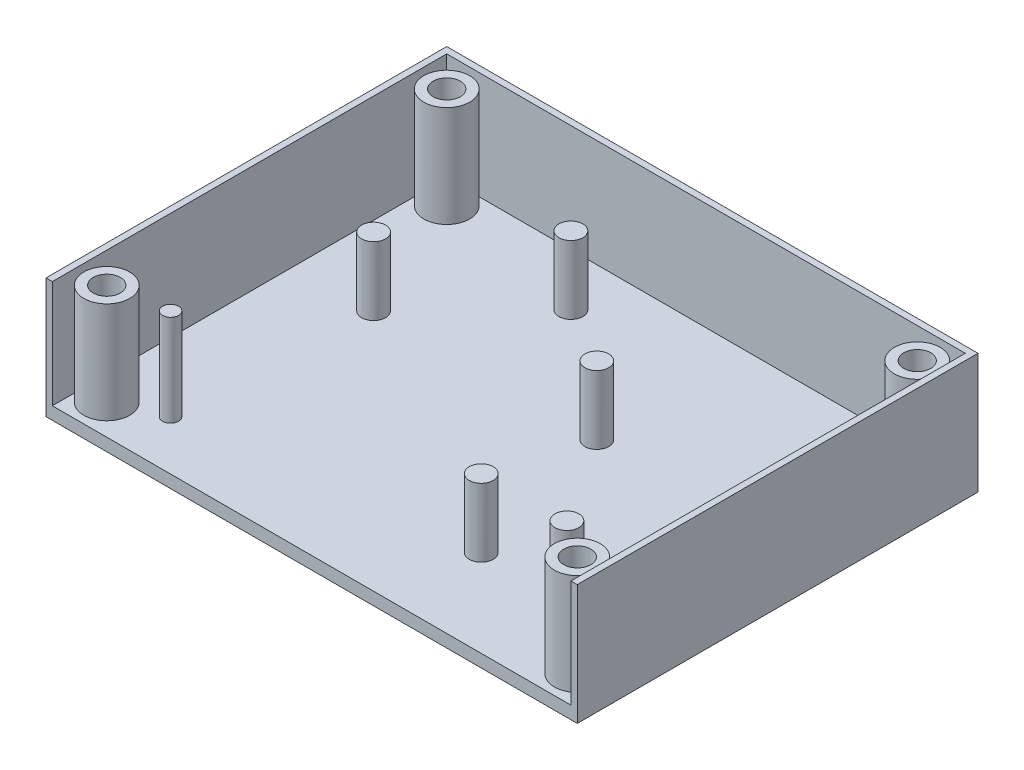
SolidWorks part; units mm, degrees
ref_plane "Front Plane" through (0, 0, 0) normal (0, 0, 1) x (1, 0, 0)
ref_plane "Top Plane" through (0, 0, 0) normal (0, 1, 0) x (1, 0, 0)
ref_plane "Right Plane" through (0, 0, 0) normal (1, 0, 0) x (0, 0, -1)
sketch "Sketch1" plane through (0, 0, 0) normal (0, 1, 0) x (1, 0, 0)
  line L0 (-66.8583, -50.2762) -> (-65.2708, -50.2762)
  line L1 (-65.2708, -50.2762) -> (64.8554, -50.2762)
  line L2 (-66.8583, -50.2762) -> (-66.8583, 50.2663)
  line L3 (-66.8583, 50.2663) -> (66.4429, 50.2663)
  line L4 (66.4429, -50.2762) -> (66.4429, 50.2663)
  line L5 (66.4429, -50.2762) -> (64.8554, -50.2762)
  line L6 (-50.3864, 41.1329) -> (-50.3864, 5.0649)
  line L7 (-50.3483, 41.1463) -> (49.9329, 41.1463)
  line L8 (-65.2708, -50.2762) -> (-65.2708, 48.6788)
  line L9 (-65.2708, 48.6788) -> (64.8554, 48.6788)
  line L10 (64.8554, -50.2762) -> (64.8554, 48.6788)
  line L11 (-50.3483, 41.1463) -> (-50.3483, -40.1162)
  line L12 (-50.3483, -40.1162) -> (49.9329, -40.1162)
  line L13 (49.9329, 41.1463) -> (49.9329, -40.1162)
  line L14 (-50.3864, 5.0649) -> (14.3836, 5.0649)
  line L15 (14.3836, 5.0649) -> (14.3836, -33.7971)
  line L16 (14.3836, -33.7971) -> (47.4036, -33.7971)
  line L17 (47.4036, -33.7971) -> (47.4036, 41.1329)
  line L18 (47.4036, 41.1329) -> (-50.3864, 41.1329)
  circle A0 centre (-59.2383, 42.6463) radius 3.4
  circle A1 centre (-59.2383, 42.6463) radius 5.75
  circle A2 centre (58.8229, 42.6463) radius 5.75
  circle A3 centre (58.8229, 42.6463) radius 3.4
  circle A4 centre (-59.2383, -42.6562) radius 5.75
  circle A5 centre (-59.2383, -42.6562) radius 3.4
  circle A6 centre (58.8229, -42.6562) radius 5.75
  circle A7 centre (58.8229, -42.6562) radius 3.4
  circle A8 centre (-21.0872, 35.6529) radius 3
  circle A9 centre (20.4128, -28.3471) radius 3
  circle A10 centre (-45.5872, 10.6529) radius 3
  circle A11 centre (10.4128, 10.6529) radius 3
  circle A12 centre (41.4128, -27.8471) radius 3
  circle A15 centre (-48.0512, -37.8237) radius 2
  point P0 (0, 0)
  dimension "D5" = 7.62
  dimension "D7" = 7.62
  dimension "D18" = 97.79
  dimension "D20" = 64.77
  dimension "D26" = 24.5
  dimension "D1" = 133.3013
  dimension "D2" = 100.5425
  dimension "D3" = 1.5875
  dimension "D4" = 1.5875
  dimension "D6" = 7.62
  dimension "D8" = 7.62
  dimension "D9" = 7.62
  dimension "D10" = 7.62
  dimension "D11" = 7.62
  dimension "D12" = 7.62
  dimension "D13" = 1.5875
  dimension "D14" = 9.12
  dimension "D15" = 16.51
  dimension "D16" = 16.51
  dimension "D17" = 81.2625
  dimension "D19" = 36.068
  dimension "D21" = 74.93
  dimension "D22" = 5.588
  dimension "D23" = 5.588
  dimension "D24" = 7.366
  dimension "D25" = 56
  dimension "D27" = 25
  dimension "D28" = 10
  dimension "D29" = 21
  dimension "D30" = 39
  dimension "D31" = 0.5
extrude "Boss-Extrude12" add sketch "Sketch1" along normal blind 3.175 contours L0 L1 L5 L4 L3 L2
extrude "Boss-Extrude13" add sketch "Sketch1<23>" along normal blind 30.1625 contours L10 L5 L4 L3 L2 L0 L8 L9 region at (-66.6913, 0, 0.005)
sketch "Sketch1<23>" plane through (0, 0, 0) normal (0, 1, 0) x (1, 0, 0) same geometry as "Sketch1"
extrude "Boss-Extrude15" add sketch "Sketch1<25>" along normal blind 28.575 contours A1 A0 | A2 A3 | A6 A7 | A4 A5 region at (-64.8257, 0, -42.6463) region at (53.2356, 0, -42.6463) region at (-64.8257, 0, 42.6562) region at (53.2356, 0, 42.6562)
sketch "Sketch1<25>" plane through (0, 0, 0) normal (0, 1, 0) x (1, 0, 0) same geometry as "Sketch1"
extrude "Cut-Extrude3" cut sketch "Sketch1<27>" along normal blind 28.575 contours A5 | A5 | A0 | A3 | A7 region at (-59.2383, 0, 42.6562)
sketch "Sketch1<27>" plane through (0, 0, 0) normal (0, 1, 0) x (1, 0, 0) same geometry as "Sketch1"
chamfer "Chamfer2" distance 1.45 angle 45 4 edges at (58.8229, 0, 46.0562) (58.8229, 0, -39.2463) (-59.2383, 0, 46.0562) (-59.2383, 0, -39.2463)
extrude "Boss-Extrude16" add sketch "Sketch1<28>" along normal blind 20.32 contours A12 | A9 | A8 | A10 | A11 region at (20.4128, 0, 28.3471) region at (41.4128, 0, 27.8471)
sketch "Sketch1<28>" plane through (0, 0, 0) normal (0, 1, 0) x (1, 0, 0) same geometry as "Sketch1"
extrude "Boss-Extrude17" add sketch "Sketch1<29>" along normal blind 26.1874 contours A15 region at (-48.0512, 0, 37.8237)
sketch "Sketch1<29>" plane through (0, 0, 0) normal (0, 1, 0) x (1, 0, 0) same geometry as "Sketch1"
